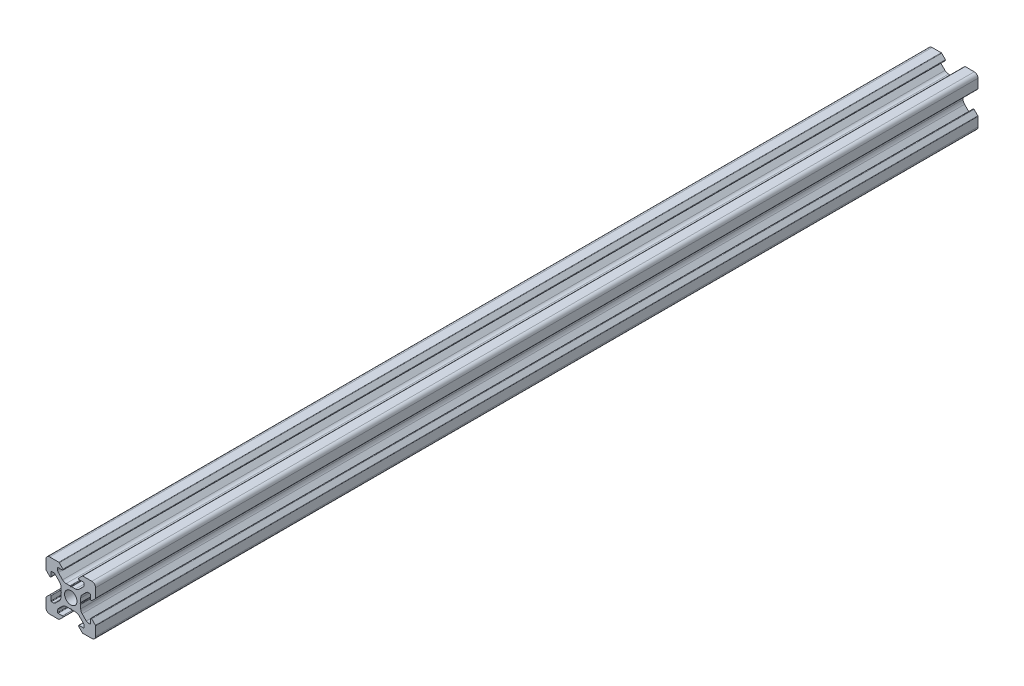
SolidWorks part; units mm, degrees
material "6063-T5"
ref_plane "Спереди" through (0, 0, 0) normal (0, 0, 1) x (1, 0, 0)
ref_plane "Сверху" through (0, 0, 0) normal (0, 1, 0) x (1, 0, 0)
ref_plane "Справа" through (0, 0, 0) normal (1, 0, 0) x (0, 0, -1)
sketch "Model" plane through (0, 0, 0) normal (0, 0, 1) x (1, 0, 0)
  line L0 (-4, 0.3377) -> (-4, 1.8988)
  line L1 (-4.5858, 3.313) -> (-6.2799, 5.0071)
  line L2 (-6.987, 5.3) -> (-7.8, 5.3)
  line L3 (-8, 5.1) -> (-8, 3.33)
  line L4 (-9.9268, 4.6532) -> (-8.4268, 3.1532)
  line L5 (-10, 4.83) -> (-10, 8.5)
  line L6 (-4.6532, 9.9268) -> (-3.1532, 8.4268)
  line L7 (-0.1815, 3.9452) -> (0, 3.8)
  line L8 (0.1815, 3.9452) -> (0, 3.8)
  line L9 (0.3377, 4) -> (1.8988, 4)
  line L10 (3.313, 4.5858) -> (5.0071, 6.2799)
  line L11 (5.3, 6.987) -> (5.3, 7.8)
  line L12 (5.1, 8) -> (3.33, 8)
  line L13 (4.6532, 9.9268) -> (3.1532, 8.4268)
  line L14 (4.83, 10) -> (8.5, 10)
  line L15 (10, 4.83) -> (10, 8.5)
  line L16 (9.9268, 4.6532) -> (8.4268, 3.1532)
  line L17 (8, 5.1) -> (8, 3.33)
  line L18 (6.987, 5.3) -> (7.8, 5.3)
  line L19 (4.5858, 3.313) -> (6.2799, 5.0071)
  line L20 (4, 0.3377) -> (4, 1.8988)
  line L21 (3.9452, 0.1815) -> (3.8, 0)
  line L22 (3.9452, -0.1815) -> (3.8, 0)
  line L23 (4, -0.3377) -> (4, -1.8988)
  line L24 (4.5858, -3.313) -> (6.2799, -5.0071)
  line L25 (6.987, -5.3) -> (7.8, -5.3)
  line L26 (8, -5.1) -> (8, -3.33)
  line L27 (9.9268, -4.6532) -> (8.4268, -3.1532)
  line L28 (10, -4.83) -> (10, -8.5)
  line L29 (4.83, -10) -> (8.5, -10)
  line L30 (4.6532, -9.9268) -> (3.1532, -8.4268)
  line L31 (5.1, -8) -> (3.33, -8)
  line L32 (5.3, -6.987) -> (5.3, -7.8)
  line L33 (3.313, -4.5858) -> (5.0071, -6.2799)
  line L34 (0.3377, -4) -> (1.8988, -4)
  line L35 (0.1815, -3.9452) -> (0, -3.8)
  line L36 (-0.1815, -3.9452) -> (0, -3.8)
  line L37 (-3.313, -4.5858) -> (-5.0071, -6.2799)
  line L38 (-5.3, -6.987) -> (-5.3, -7.8)
  line L39 (-5.1, -8) -> (-3.33, -8)
  line L40 (-4.6532, -9.9268) -> (-3.1532, -8.4268)
  line L41 (-4.83, -10) -> (-8.5, -10)
  line L42 (-10, -4.83) -> (-10, -8.5)
  line L43 (-9.9268, -4.6532) -> (-8.4268, -3.1532)
  line L44 (-8, -5.1) -> (-8, -3.33)
  line L45 (-6.987, -5.3) -> (-7.8, -5.3)
  line L46 (-4.5858, -3.313) -> (-6.2799, -5.0071)
  line L47 (-4, -0.3377) -> (-4, -1.8988)
  line L48 (-3.9452, -0.1815) -> (-3.8, 0)
  line L49 (-3.9452, 0.1815) -> (-3.8, 0)
  line L50 (-0.3377, -4) -> (-1.8988, -4)
  line L51 (-0.3377, 4) -> (-1.8988, 4)
  line L52 (-3.313, 4.5858) -> (-5.0071, 6.2799)
  line L53 (-5.3, 6.987) -> (-5.3, 7.8)
  line L54 (-5.1, 8) -> (-3.33, 8)
  line L55 (-4.83, 10) -> (-8.5, 10)
  arc A0 (-4, 0.3377) -> (-3.9452, 0.1815) centre (-3.75, 0.3377) ccw
  arc A1 (-4, 1.8988) -> (-4.5858, 3.313) centre (-6, 1.8988) ccw
  arc A2 (-6.2799, 5.0071) -> (-6.987, 5.3) centre (-6.987, 4.3) ccw
  arc A3 (-7.8, 5.3) -> (-8, 5.1) centre (-7.8, 5.1) ccw
  arc A4 (-8.4268, 3.1532) -> (-8, 3.33) centre (-8.25, 3.33) ccw
  arc A5 (-10, 4.83) -> (-9.9268, 4.6532) centre (-9.75, 4.83) ccw
  arc A6 (-8.5, 10) -> (-10, 8.5) centre (-8.5, 8.5) ccw
  arc A7 (-4.6532, 9.9268) -> (-4.83, 10) centre (-4.83, 9.75) ccw
  arc A8 (-3.33, 8) -> (-3.1532, 8.4268) centre (-3.33, 8.25) ccw
  arc A9 (-5.1, 8) -> (-5.3, 7.8) centre (-5.1, 7.8) ccw
  arc A10 (-5.3, 6.987) -> (-5.0071, 6.2799) centre (-4.3, 6.987) ccw
  arc A11 (-3.313, 4.5858) -> (-1.8988, 4) centre (-1.8988, 6) ccw
  arc A12 (-0.1815, 3.9452) -> (-0.3377, 4) centre (-0.3377, 3.75) ccw
  arc A13 (0.3377, 4) -> (0.1815, 3.9452) centre (0.3377, 3.75) ccw
  arc A14 (1.8988, 4) -> (3.313, 4.5858) centre (1.8988, 6) ccw
  arc A15 (5.0071, 6.2799) -> (5.3, 6.987) centre (4.3, 6.987) ccw
  arc A16 (5.3, 7.8) -> (5.1, 8) centre (5.1, 7.8) ccw
  arc A17 (3.1532, 8.4268) -> (3.33, 8) centre (3.33, 8.25) ccw
  arc A18 (4.83, 10) -> (4.6532, 9.9268) centre (4.83, 9.75) ccw
  arc A19 (10, 8.5) -> (8.5, 10) centre (8.5, 8.5) ccw
  arc A20 (9.9268, 4.6532) -> (10, 4.83) centre (9.75, 4.83) ccw
  arc A21 (8, 3.33) -> (8.4268, 3.1532) centre (8.25, 3.33) ccw
  arc A22 (8, 5.1) -> (7.8, 5.3) centre (7.8, 5.1) ccw
  arc A23 (6.987, 5.3) -> (6.2799, 5.0071) centre (6.987, 4.3) ccw
  arc A24 (4.5858, 3.313) -> (4, 1.8988) centre (6, 1.8988) ccw
  arc A25 (3.9452, 0.1815) -> (4, 0.3377) centre (3.75, 0.3377) ccw
  arc A26 (4, -0.3377) -> (3.9452, -0.1815) centre (3.75, -0.3377) ccw
  arc A27 (4, -1.8988) -> (4.5858, -3.313) centre (6, -1.8988) ccw
  arc A28 (6.2799, -5.0071) -> (6.987, -5.3) centre (6.987, -4.3) ccw
  arc A29 (7.8, -5.3) -> (8, -5.1) centre (7.8, -5.1) ccw
  arc A30 (8.4268, -3.1532) -> (8, -3.33) centre (8.25, -3.33) ccw
  arc A31 (10, -4.83) -> (9.9268, -4.6532) centre (9.75, -4.83) ccw
  arc A32 (8.5, -10) -> (10, -8.5) centre (8.5, -8.5) ccw
  arc A33 (4.6532, -9.9268) -> (4.83, -10) centre (4.83, -9.75) ccw
  arc A34 (3.33, -8) -> (3.1532, -8.4268) centre (3.33, -8.25) ccw
  arc A35 (5.1, -8) -> (5.3, -7.8) centre (5.1, -7.8) ccw
  arc A36 (5.3, -6.987) -> (5.0071, -6.2799) centre (4.3, -6.987) ccw
  arc A37 (3.313, -4.5858) -> (1.8988, -4) centre (1.8988, -6) ccw
  arc A38 (0.1815, -3.9452) -> (0.3377, -4) centre (0.3377, -3.75) ccw
  arc A39 (-0.3377, -4) -> (-0.1815, -3.9452) centre (-0.3377, -3.75) ccw
  arc A40 (-1.8988, -4) -> (-3.313, -4.5858) centre (-1.8988, -6) ccw
  arc A41 (-5.0071, -6.2799) -> (-5.3, -6.987) centre (-4.3, -6.987) ccw
  arc A42 (-5.3, -7.8) -> (-5.1, -8) centre (-5.1, -7.8) ccw
  arc A43 (-3.1532, -8.4268) -> (-3.33, -8) centre (-3.33, -8.25) ccw
  arc A44 (-4.83, -10) -> (-4.6532, -9.9268) centre (-4.83, -9.75) ccw
  arc A45 (-10, -8.5) -> (-8.5, -10) centre (-8.5, -8.5) ccw
  arc A46 (-9.9268, -4.6532) -> (-10, -4.83) centre (-9.75, -4.83) ccw
  arc A47 (-8, -3.33) -> (-8.4268, -3.1532) centre (-8.25, -3.33) ccw
  arc A48 (-8, -5.1) -> (-7.8, -5.3) centre (-7.8, -5.1) ccw
  arc A49 (-6.987, -5.3) -> (-6.2799, -5.0071) centre (-6.987, -4.3) ccw
  arc A50 (-4.5858, -3.313) -> (-4, -1.8988) centre (-6, -1.8988) ccw
  arc A51 (-3.9452, -0.1815) -> (-4, -0.3377) centre (-3.75, -0.3377) ccw
  circle A52 centre (0, 0) radius 2.5
extrude "Extrude body" add sketch "Model" along normal blind 356
